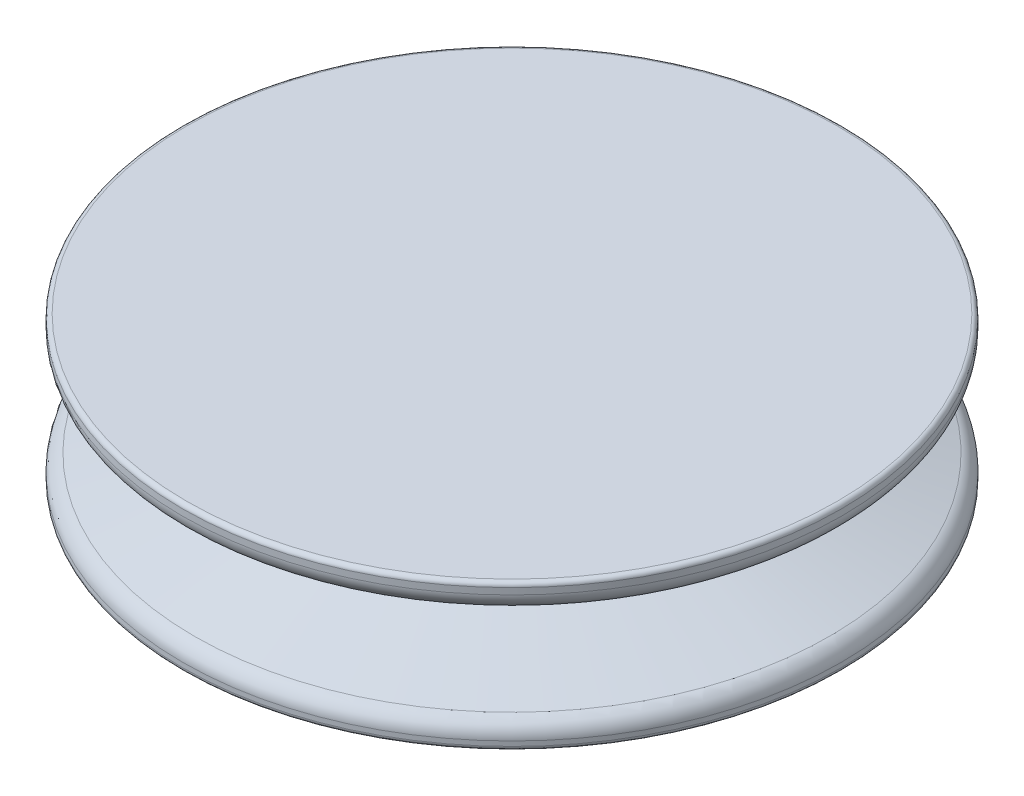
SolidWorks part; units mm, degrees
ref_plane "Front Plane" through (0, 0, 0) normal (0, 0, 1) x (1, 0, 0)
ref_plane "Top Plane" through (0, 0, 0) normal (0, 1, 0) x (1, 0, 0)
ref_plane "Right Plane" through (0, 0, 0) normal (1, 0, 0) x (0, 0, -1)
sketch "Sketch2" plane through (0, 0, 0) normal (0, 0, 1) x (1, 0, 0)
  line L0 (0, 0) -> (0, 29.0272) construction
  line L1 (0, 0) -> (-76.2, 0)
  line L2 (-76.2, 0) -> (-76.2, -6.3)
  line L3 (-76.2, -6.3) -> (0, -9.627)
  line L4 (0, 0) -> (0, -9.627)
  dimension "D1" = 6.3
  dimension "D2" = 2.5
  dimension "D3" = 152.4
revolve "Revolve1" add sketch "Sketch2" angle 360 about L0
sketch "Sketch3" plane through (0, 0, 0) normal (0, 1, 0) x (1, 0, 0)
  circle A0 centre (0, 0) radius 20
  dimension "D1" = 40
extrude "Boss-Extrude1" add sketch "Sketch3" against normal blind 12.5
sketch "Sketch4" plane through (0, 0, 0) normal (0, 0, 1) x (1, 0, 0)
  line L0 (-26, -12.5) -> (0, -12.5)
  line L2 (-26, -12.5) -> (-76.2, -28.811)
  line L3 (-76.2, -28.811) -> (-76.2, -33.8)
  line L4 (76.2, 0) -> (-76.2, 0) construction
  line L5 (-76.2, 0) -> (-76.2, -6.3) construction
  line L6 (-20, -12.5) -> (20, -12.5) construction
  line L7 (-73.6, -30.7) -> (-73.6, -33.8)
  line L8 (-25.5882, -15.1) -> (-73.6, -30.7)
  line L9 (-25.5882, -15.1) -> (0, -15.1)
  line L10 (0, -15.1) -> (0, -12.5)
  line L11 (-76.2, -33.8) -> (-73.6, -33.8)
  line L12 (0, 0) -> (0, 20.8924) construction
  dimension "D1" = 18
  dimension "D2" = 33.8
  dimension "D3" = 26
  dimension "D4" = 2.6
revolve "Revolve2" add sketch "Sketch4" angle 360 about L12
fillet "Fillet1" radius 4 2 edges at (0, -28.811, -76.2) (0, -6.3, -76.2)
fillet "Fillet2" radius 1 3 edges at (0, 0, -76.2) (0, -33.8, -73.6) (0, -33.8, -76.2)
fillet "Fillet3" radius 2.4 1 edges at (0, -30.7, -73.6)
fillet "Fillet4" radius 10 1 edges at (0, -12.5, -26)
sketch "Sketch5" plane through (0, -15.1, 0) normal (0, -1, 0) x (1, 0, 0)
  circle A0 centre (0, 0) radius 42.1
  dimension "D1" = 84.2
extrude "Boss-Extrude2" add sketch "Sketch5" against normal up to surface (33.635 mm away) from offset 39 up to face at (0, -30.1611, -71.9416)
chamfer "Chamfer1" distance 2 angle 80 1 edges at (0, -54.1, -42.1) first distance on face at (0, -54.1, -42.1)
fillet "Fillet5" radius 2 1 edges at (0, -52.1, -42.1)
sketch "Sketch6" plane through (0, -54.1, 0) normal (0, -1, 0) x (1, 0, 0)
  circle A0 centre (0, 0) radius 19.5
  dimension "D1" = 39
extrude "Cut-Extrude1" cut sketch "Sketch6" against normal blind 2.3
sketch "Sketch7" plane through (0, -51.8, 0) normal (0, -1, 0) x (1, 0, 0)
  line L1 (-6.8849, 11.925) -> (-13.7698, 0)
  line L2 (-13.7698, 0) -> (-6.8849, -11.925)
  line L3 (-6.8849, -11.925) -> (6.8849, -11.925)
  line L4 (6.8849, -11.925) -> (13.7698, 0)
  line L5 (13.7698, 0) -> (6.8849, 11.925)
  line L6 (6.8849, 11.925) -> (-6.8849, 11.925)
  circle A0 centre (0, 0) radius 11.925 construction
  dimension "D1" = 23.85
extrude "Boss-Extrude3" add sketch "Sketch7" along normal blind 14.6
sketch "Sketch8" plane through (0, -66.4, 0) normal (0, -1, 0) x (1, 0, 0)
  circle A0 centre (0, 0) radius 7.3
  dimension "D1" = 14.6
extrude "Boss-Extrude4" add sketch "Sketch8" along normal blind 2
chamfer "Chamfer2" distance 1 angle 45 1 edges at (0, -68.4, -7.3)
chamfer "Chamfer3" distance 1 angle 45 6 edges at (0, -66.4, 11.925) (10.3274, -66.4, 5.9625) (10.3274, -66.4, -5.9625) (0, -66.4, -11.925) (-10.3274, -66.4, 5.9625) (-10.3274, -66.4, -5.9625)
fillet "Fillet6" radius 0.5 1 edges at (0, -54.1, -19.5)
fillet "Fillet7" radius 1 2 edges at (0, -12.5, -20) (0, -8.7537, 20)
ref_plane "Plane1" through (0, -9.711, 0) normal (0, 1, 0) x (1, 0, 0)
